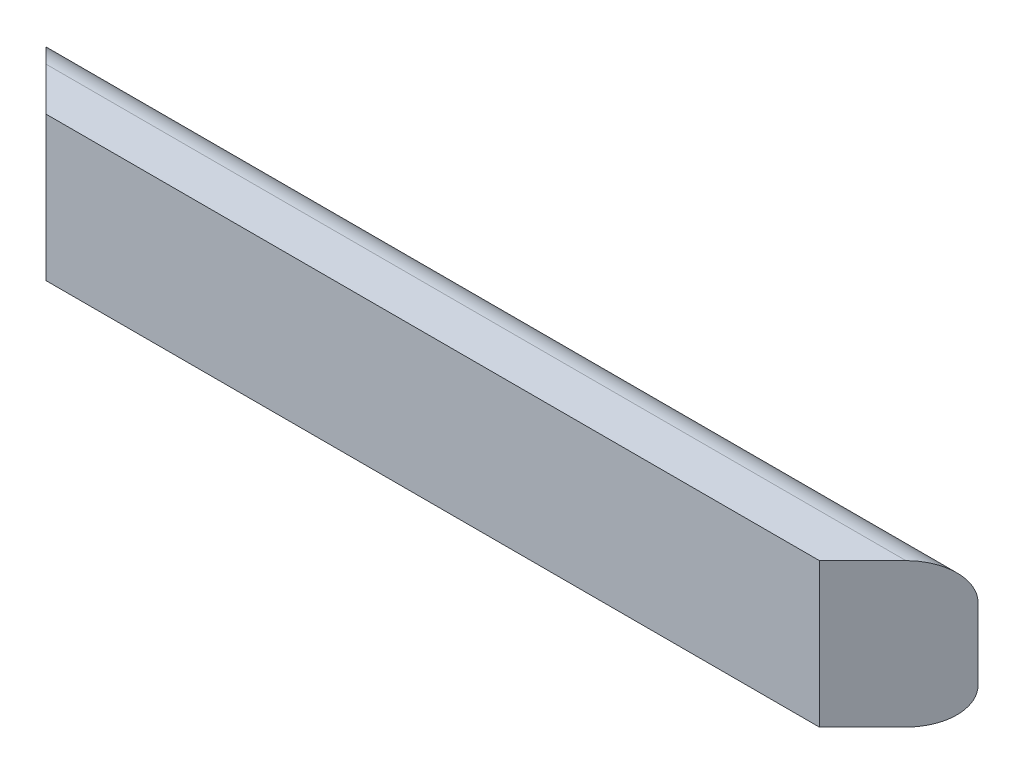
SolidWorks part; units mm, degrees
ref_plane "Front Plane" through (0, 0, 0) normal (0, 0, 1) x (1, 0, 0)
ref_plane "Top Plane" through (0, 0, 0) normal (0, 1, 0) x (1, 0, 0)
ref_plane "Right Plane" through (0, 0, 0) normal (1, 0, 0) x (0, 0, -1)
sketch "Sketch1" plane through (0, 0, 0) normal (1, 0, 0) x (0, 0, -1)
  line L0 (6.35, 127) -> (38.1, 127)
  line L1 (0, 0) -> (6.35, 0)
  line L2 (0, 0) -> (0, 127)
  line L3 (0, 127) -> (6.35, 127)
  line L5 (69.85, 95.25) -> (69.85, 31.75)
  line L6 (38.1, 0) -> (6.35, 0)
  arc A0 (69.85, 95.25) -> (38.1, 127) centre (38.1, 95.25) ccw
  arc A1 (38.1, 0) -> (69.85, 31.75) centre (38.1, 31.75) ccw
  dimension "D3" = 63.5
  dimension "D5" = 31.75
  dimension "D1" = 127
  dimension "D2" = 6.35
  dimension "D4" = 31.75
extrude "Boss-Extrude1" add sketch "Sketch1" along normal blind 410.337 and the other way blind 410.337
sketch "Sketch2" plane through (0, 127, 0) normal (0, 1, 0) x (1, 0, 0)
  line L0 (410.337, 69.85) -> (340.487, 0)
  line L1 (-69.85, 0) -> (69.85, 0) construction
  line L2 (-410.337, 69.85) -> (-340.487, 0)
  line L3 (-410.337, 69.85) -> (-410.337, 0)
  line L4 (-410.337, 38.1) -> (-410.337, 0) construction
  line L5 (-410.337, 0) -> (-340.487, 0)
  line L6 (410.337, 69.85) -> (410.337, 0)
  line L7 (410.337, 38.1) -> (410.337, 0) construction
  line L8 (410.337, 0) -> (340.487, 0)
  dimension "D1" = 45
  dimension "D2" = 45
extrude "Cut-Extrude1" cut sketch "Sketch2" against normal through all
